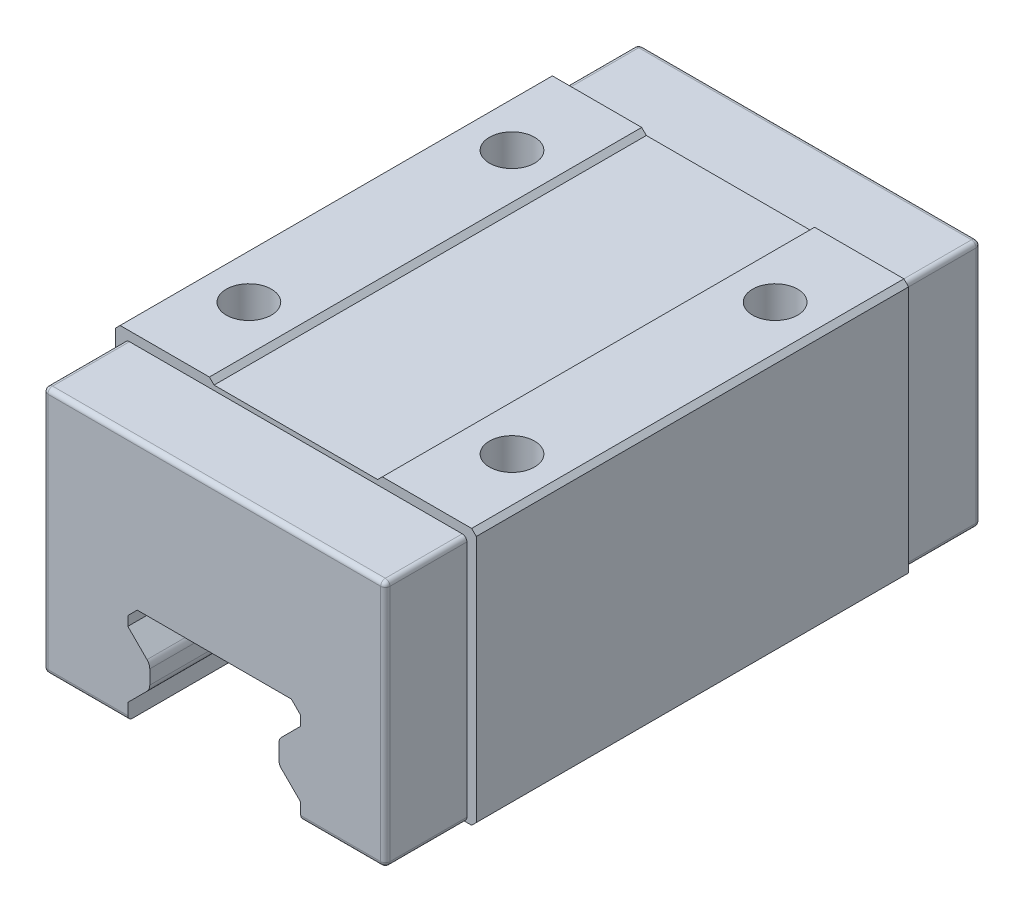
SolidWorks part; units mm, degrees
material "AISI Type A2 Tool Steel"
ref_plane "Front Plane" through (0, 0, 0) normal (0, 0, 1) x (1, 0, 0)
ref_plane "Top Plane" through (0, 0, 0) normal (0, 1, 0) x (1, 0, 0)
ref_plane "Right Plane" through (0, 0, 0) normal (1, 0, 0) x (0, 0, -1)
sketch "Sketch1" plane through (0, 0, 0) normal (0, 0, 1) x (1, 0, 0)
  line L1 (-24, 5.8) -> (24, 5.8)
  line L2 (-24, 5.8) -> (-24, 40)
  line L3 (-24, 40) -> (24, 40)
  line L4 (24, 5.8) -> (24, 40)
  line L5 (-24, 5.8) -> (24, 40) construction
  line L6 (-24, 40) -> (24, 5.8) construction
  point P0 (0, 22.9)
  dimension "D1" = 40
  dimension "D2" = 5.8
  dimension "D3" = 48
extrude "Boss-Extrude1" add sketch "Sketch1" along normal mid plane 57.5
sketch "Sketch2" plane through (0, 0, 0) normal (0, 0, 1) x (1, 0, 0)
  line L0 (-24, 5.8) -> (24, 5.8) construction
  line L1 (-22.75, 5.8) -> (22.75, 5.8)
  line L2 (-22.75, 5.8) -> (-22.75, 38.75)
  line L3 (-22.75, 38.75) -> (22.75, 38.75)
  line L4 (22.75, 5.8) -> (22.75, 38.75)
  line L5 (-22.75, 38.75) -> (-24, 38.75) construction
  line L6 (-24, 40) -> (-24, 5.8) construction
  line L7 (22.75, 38.75) -> (22.75, 40) construction
  line L8 (24, 40) -> (-24, 40) construction
  line L9 (22.75, 38.75) -> (24, 38.75) construction
  line L10 (24, 5.8) -> (24, 40) construction
  point P9 (0, 38.75)
  dimension "D1" = 1.25
extrude "Boss-Extrude2" add sketch "Sketch2" along normal mid plane 79.2
sketch "Sketch3" plane through (0, 0, 39.6) normal (0, 0, 1) x (1, 0, 0)
  line L1 (-11.5, 19.2) -> (11.5, 19.2)
  line L2 (-11.5, 19.2) -> (-11.5, 0)
  line L3 (-11.5, 0) -> (11.5, 0)
  line L4 (11.5, 19.2) -> (11.5, 0)
  line L5 (-11.5, 19.2) -> (11.5, 0) construction
  line L6 (-11.5, 0) -> (11.5, 19.2) construction
  point P0 (0, 9.6)
  dimension "D1" = 23
  dimension "D2" = 19.2
extrude "Cut-Extrude1" cut sketch "Sketch3" against normal through all
sketch "Sketch4" plane through (0, 0, 39.6) normal (0, 0, 1) x (1, 0, 0)
  line L0 (-11.5, 16.7) -> (-11.5, 7.95)
  line L1 (-11.5, 19.2) -> (-11.5, 5.8) construction
  line L2 (-11.5, 7.95) -> (-8.5833, 10.8667)
  line L3 (-8.5833, 10.8667) -> (-8.5833, 13.7833)
  line L4 (-8.5833, 13.7833) -> (-11.5, 16.7)
  line L5 (11.5, 19.2) -> (-11.5, 19.2) construction
  line L6 (-8.5833, 13.7833) -> (-11.5, 13.7833) construction
  line L7 (-8.5833, 10.8667) -> (-11.5, 10.8667) construction
  line L8 (-10.0417, 13.7833) -> (-10.0417, 10.8667) construction
  line L9 (0, 0) -> (0, 19.2) construction
  line L10 (10.0417, 13.7833) -> (10.0417, 10.8667) construction
  line L11 (8.5833, 10.8667) -> (11.5, 10.8667) construction
  line L12 (8.5833, 13.7833) -> (11.5, 13.7833) construction
  line L13 (8.5833, 13.7833) -> (11.5, 16.7)
  line L14 (8.5833, 10.8667) -> (8.5833, 13.7833)
  line L15 (11.5, 7.95) -> (8.5833, 10.8667)
  line L16 (11.5, 16.7) -> (11.5, 7.95)
  dimension "D1" = 2.5
  dimension "D2" = 8.75
extrude "Boss-Extrude3" add sketch "Sketch4" against normal up to surface (79.2 mm away) up to face at (0, 17.3875, -39.6)
chamfer "Chamfer1" distance 1.25 angle 45 2 edges at (11.5, 19.2, 0) (-11.5, 19.2, 0)
fillet "Fillet1" radius 1.25 4 edges at (8.5833, 10.8667, 0) (8.5833, 13.7833, 0) (-8.5833, 10.8667, 0) (-8.5833, 13.7833, 0)
sketch "Sketch5" plane through (0, 0, 28.75) normal (0, 0, 1) x (1, 0, 0)
  line L0 (24, 40) -> (-24, 40) construction
  line L1 (-11.5, 40) -> (11.5, 40)
  line L2 (-11.5, 40) -> (-11.5, 39.38)
  line L3 (-11.5, 39.38) -> (11.5, 39.38)
  line L4 (11.5, 40) -> (11.5, 39.38)
  point P6 (0, 39.38)
  dimension "D1" = 23
  dimension "D2" = 0.62
extrude "Cut-Extrude2" cut sketch "Sketch5" against normal through all
chamfer "Chamfer2" distance 0.62 angle 45 6 edges at (24, 40, 0) (24, 5.8, 0) (-24, 5.8, 0) (-24, 40, 0) (11.5, 39.38, 0) (-11.5, 39.38, 0)
fillet "Fillet2" radius 0.62 16 edges at (-22.75, 5.8, -34.175) (-17.125, 5.8, -39.6) (-22.75, 5.8, 34.175) (-17.125, 5.8, 39.6) (22.75, 5.8, 34.175) (-22.75, 22.275, 39.6) (-22.75, 38.75, 34.175) (22.75, 38.75, 34.175) (22.75, 22.275, 39.6) (0, 38.75, 39.6) (22.75, 5.8, -34.175) (22.75, 22.275, -39.6) (22.75, 38.75, -34.175) (-22.75, 38.75, -34.175) (-22.75, 22.275, -39.6) (0, 38.75, -39.6)
sketch "Sketch6" plane through (0, 40, 0) normal (0, 1, 0) x (1, 0, 0)
  line L1 (0, 0) -> (17.5, -17.5) construction
  line L3 (0, 0) -> (-17.5, -17.5) construction
  circle A1 centre (-17.5, -17.5) radius 3
  circle A2 centre (17.5, -17.5) radius 3
  dimension "D1" = 6
  dimension "D2" = 35
  dimension "D3" = 17.5
extrude "Cut-Extrude3" cut sketch "Sketch6" against normal blind 9
mirror "Mirror1" about plane through (0, 0, 0) normal (0, 0, 1) of "Cut-Extrude3"
sketch "Sketch7" plane through (0, 0, 0) normal (0, 0, 1) x (1, 0, 0)
  line L0 (-23.38, 40) -> (-35, 40)
  line L1 (-35, 40) -> (-35, 30)
  line L2 (-23.38, 40) -> (-23.38, 19.62)
  line L3 (-24, 39.38) -> (-24, 6.42) construction
  line L4 (-24, 19.62) -> (-23.38, 19.62)
  line L5 (-35, 30) -> (-34.38, 30)
  line L6 (0, 0) -> (0, 39.38) construction
  line L7 (-10.88, 39.38) -> (10.88, 39.38) construction
  line L8 (35, 30) -> (34.38, 30)
  line L9 (24, 19.62) -> (23.38, 19.62)
  line L10 (23.38, 40) -> (23.38, 19.62)
  line L11 (35, 40) -> (35, 30)
  line L12 (23.38, 40) -> (35, 40)
  arc A1 (-34.38, 30) -> (-24, 19.62) centre (-34.38, 19.62) cw
  arc A2 (34.38, 30) -> (24, 19.62) centre (34.38, 19.62) ccw
  point P22 (-34.69, 30)
  dimension "D1" = 70
  dimension "D2" = 10
  dimension "D3" = 0.62
extrude "Boss-Extrude4" [suppressed] add sketch "Sketch7" along normal mid plane 30
sketch "Sketch8" [suppressed] plane through (0, 0, 0) normal (0, 0, 1) x (1, 0, 0)
  line L5 (-35, 30) -> (-35, 40)
  line L6 (-35, 30) -> (-23.38, 30)
  line L7 (-35, 40) -> (-23.38, 40)
  line L8 (-23.38, 30) -> (-23.38, 40)
  line L9 (35, 30) -> (35, 40)
  line L10 (35, 30) -> (23.38, 30)
  line L11 (35, 40) -> (23.38, 40)
  line L13 (23.38, 40) -> (23.38, 30)
extrude "Boss-Extrude5" [suppressed] add sketch "Sketch8" along normal mid plane 57.5
chamfer "Chamfer3" [suppressed] distance 0.62 angle 45
fillet "Fillet3" [suppressed] radius 6
equation "\"D2@Sketch4\"=\"D1@Sketch4\"*3.5"
